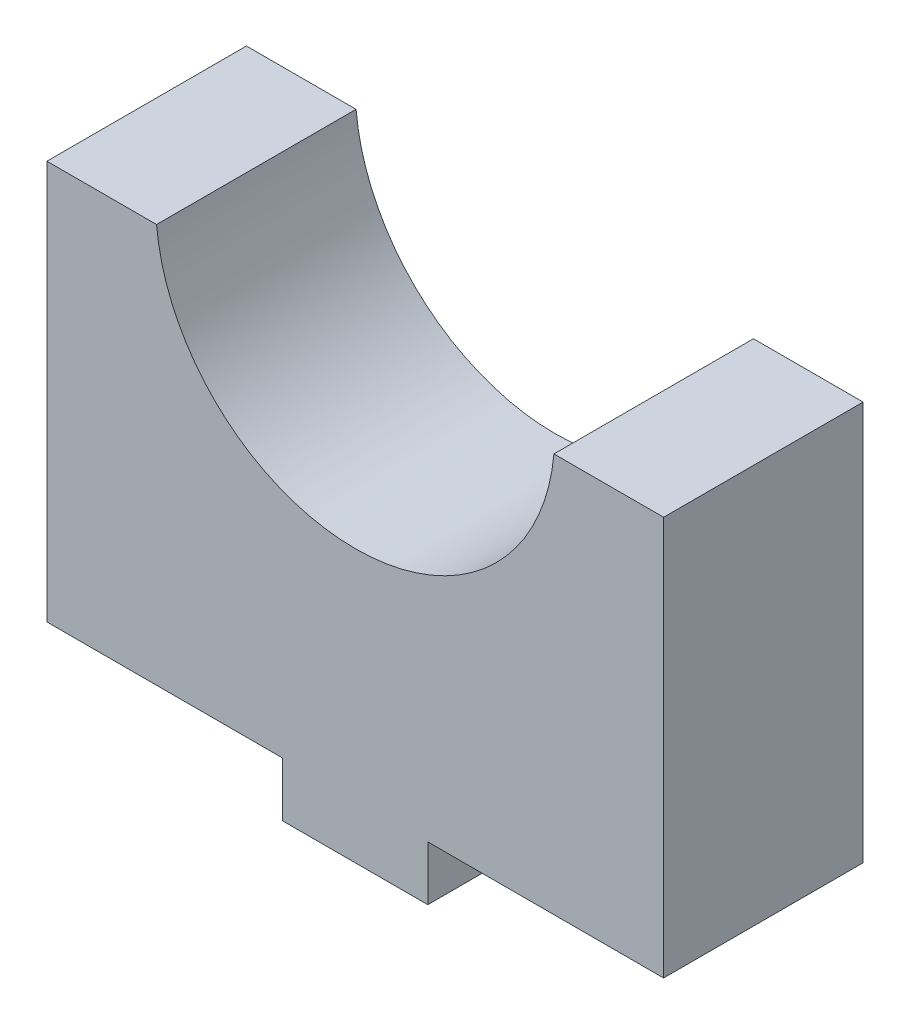
SolidWorks part; units mm, degrees
ref_plane "Front Plane" through (0, 0, 0) normal (0, 0, 1) x (1, 0, 0)
ref_plane "Top Plane" through (0, 0, 0) normal (0, 1, 0) x (1, 0, 0)
ref_plane "Right Plane" through (0, 0, 0) normal (1, 0, 0) x (0, 0, -1)
sketch "Sketch1" plane through (0, 0, 0) normal (0, 0, 1) x (1, 0, 0)
  line L0 (-17, 0) -> (17, 0) construction
  line L1 (0, 0) -> (0, -11) construction
  line L2 (-17, -1) -> (17, -1)
  line L4 (-17, -1) -> (-17, -23)
  line L5 (-17, -23) -> (17, -23)
  line L6 (17, -23) -> (17, -1)
  circle A0 centre (0, 0) radius 11
  dimension "D1" = 22
  dimension "D2" = 17
  dimension "D5" = 22
  dimension "D3" = 1
extrude "Boss-Extrude1" add sketch "Sketch1" along normal blind 11 contours A0 L2 L4 L5 L6 region at (0, -13.9672, 0)
sketch "Sketch2" plane through (0, -23, 0) normal (0, -1, 0) x (1, 0, 0)
  line L1 (4, 0) -> (-4, 0)
  line L3 (4, 11) -> (-4, 11)
  line L4 (-4, 0) -> (-4, 11)
  line L5 (-17, 11) -> (17, 11) construction
  line L6 (4, 0) -> (4, 11)
  point P4 (-0.374, 4.2257)
  point P5 (-1.0687, 1.928)
  dimension "D1" = 8
  dimension "D2" = 11
  dimension "D3" = 4
  dimension "D4" = 4
extrude "Boss-Extrude2" add sketch "Sketch2" along normal blind 3
